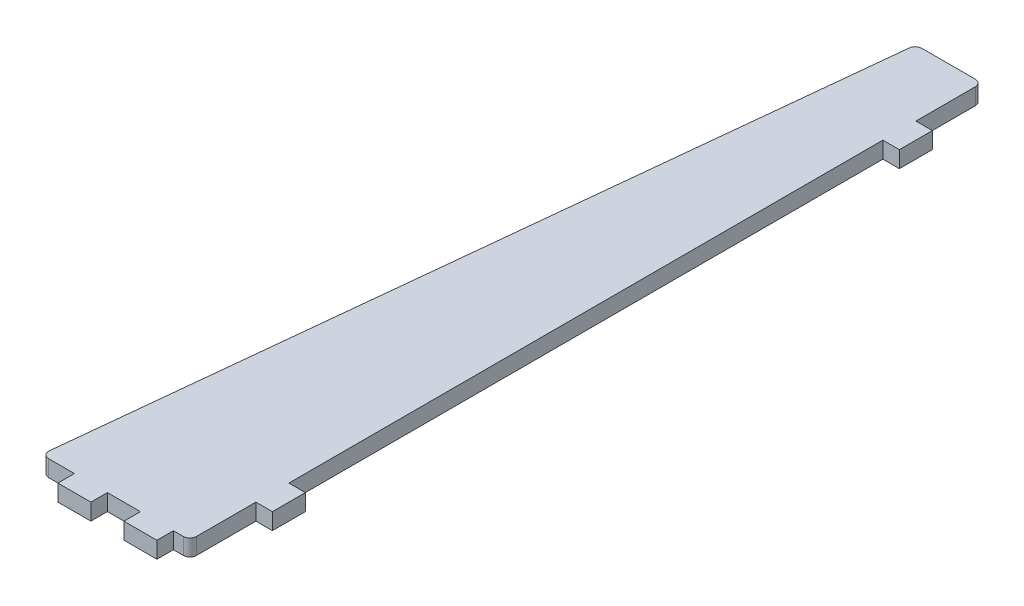
SolidWorks part; units mm, degrees
material "Beech"
ref_plane "Front Plane" through (0, 0, 0) normal (0, 0, 1) x (1, 0, 0)
ref_plane "Top Plane" through (0, 0, 0) normal (0, 1, 0) x (1, 0, 0)
ref_plane "Right Plane" through (0, 0, 0) normal (1, 0, 0) x (0, 0, -1)
sketch "Sketch1" plane through (0, 0, 0) normal (0, 1, 0) x (1, 0, 0)
  line L0 (0, 0) -> (12.7, 0)
  line L1 (12.7, 0) -> (12.7, -6.35)
  line L2 (12.7, -6.35) -> (25.4, -6.35)
  line L3 (25.4, -6.35) -> (25.4, 0)
  line L4 (25.4, 0) -> (38.1, 0)
  line L5 (38.1, 0) -> (38.1, -6.35)
  line L6 (38.1, -6.35) -> (50.8, -6.35)
  line L7 (50.8, -6.35) -> (50.8, 0)
  line L8 (50.8, 0) -> (57.15, 0)
  line L9 (57.15, 0) -> (57.15, 25.4)
  line L10 (57.15, 304.8) -> (31.75, 304.8)
  line L11 (31.75, 304.8) -> (0, 0)
  line L12 (57.15, 25.4) -> (63.5, 25.4)
  line L13 (63.5, 25.4) -> (63.5, 38.1)
  line L14 (63.5, 38.1) -> (57.15, 38.1)
  line L15 (57.15, 38.1) -> (57.15, 266.7)
  line L16 (57.15, 266.7) -> (63.5, 266.7)
  line L17 (63.5, 266.7) -> (63.5, 279.4)
  line L18 (63.5, 279.4) -> (57.15, 279.4)
  line L19 (57.15, 279.4) -> (57.15, 304.8)
  dimension "D1" = 12.7
  dimension "D2" = 6.35
  dimension "D3" = 25.4
  dimension "D4" = 25.4
  dimension "D5" = 12.7
  dimension "D6" = 304.8
  dimension "D7" = 25.4
  dimension "D8" = 25.4
  dimension "D9" = 6.35
extrude "Side Plate" add sketch "Sketch1" along normal blind 6.35
fillet "Fillet1" radius 2.54 4 edges at (57.15, 3.175, 0) (57.15, 3.175, -304.8) (31.75, 3.175, -304.8) (0, 3.175, 0)
equation "\"CageLeftBottomEdge\"=22.11mm"
equation "\"CageLeftTopEdge\"=22.11mm"
equation "\"CageRightBottomEdge\"=21.63mm"
equation "\"CageRightTopEdge\"=21.63mm"
equation "\"CageHeight\"=86.04mm"
equation "\"CageLength\"=73.76mm"
equation "\"CageTopScrewClearance\"=10mm"
equation "\"CageBottomScrewClearance\"=25mm"
equation "\"CageLeftTopDepth\"= 11.65mm"
equation "\"CageLeftBottomDepth\"=11.11mm"
equation "\"CageLeftTopHeight\"=8.56175mm"
equation "\"CageLeftBottomHeight\"=16mm"
equation "\"CageRightTopDepth\"= 11.05mm"
equation "\"CageRightBottomDepth\"=10.58mm"
equation "\"CageRightTopHeight\"=9.6mm"
equation "\"CageRightBottomHeight\"=15.49mm"
equation "\"CageLeftTopChannelDepth\"=2.41908mm"
equation "\"CageLeftBottomChannelDepth\"=2.588mm"
equation "\"CageLeftChannelHeight\"=11.7mm"
equation "\"CageRightTopChannelDepth\"=2.32mm"
equation "\"CageRightBottomChannelDepth\"=2.318mm"
equation "\"CageRightChannelHeight\"=10mm"
equation "\"CageChanRelHeight\"=23.99mm"
equation "\"CageChanRelDepth\"=5.492mm"
equation "\"CageChamberRadius\"=16.261mm"
equation "\"CageScrewDiameter\"=4.8mm"
equation "\"CageSetScrewDiameter\"=3.5mm"
equation "\"CageAxleRadius\"=6.639mm"
equation "\"CageAxleKeyHeight\"=1.619mm"
equation "\"CageAxleKeyWidth\"=2.662mm"
equation "\"CageHoseWindowWidth\"=16.29mm"
equation "\"CageHoseWindowHeight\"=26.5mm"
equation "\"CageHoseWindow-Edge\"=8.89mm"
equation "\"CageScrew-VerticalEdge\"=5.0mm"
equation "\"CageScrew-HorizontalEdge\"=7.5mm"
equation "\"CageScrew-HoseCornerScrewEdge\"=4.45mm"
equation "\"CageAxle-BottomEdge\"=56.05mm"
equation "\"CageAxle-FrontEdge\"=46.03mm"
equation "\"CageBackSetScrew-Axle\"=40mm"
equation "\"CageFrontSetScrew-Axle\"=22mm"
equation "\"CageVelocityWindow-BackEdge\"=34.8mm"
equation "\"CageVelocityWindow-BottomEdge\"=27.55mm"
equation "\"CageVelocityWindowHeight\"=22.29mm"
equation "\"CageVelocityWindowWidth\"=12.61mm"
equation "\"TriggerSlot-BottomEdge\"=6.35mm"
equation "\"TriggerSlot-FrontEdge\"=15mm"
equation "\"TriggerSlotSize\"=6.7mm"
equation "\"TriggerRackOffset\"=.236224in"
equation "\"TriggerSlotSizeInt\"=.25in"
equation "\"MotorMountLegLength\"=.25in"
equation "\"GearOffset\"=.264907in"
equation "\"TriggerSlotSpacing\"=.25in"
equation "\"TriggerMiniSlotWidth\"=3.5mm"
equation "\"TriggerRackWidth\"=6.5mm"
equation "\"whitemotordepth\"=11.27mm"
equation "\"whitemotorbackdepth\"=3.845mm"
equation "\"whitemotoraxledepth\" = 3.5mm"
equation "\"whitemotoraxleoffset\"=11.4mm"
equation "\"whitemotorwidth\"=12.07mm"
equation "\"whitemotorheight\"=16.68mm"
equation "\"whitemotorcylinderlength\" =13.04mm"
equation "\"whitemotorcylinderradius\"=3.845mm"
equation "\"whitemotorcylinderoffset\"=2.35mm"
equation "\"whitemotorcutoutlength\"=1.88mm"
equation "\"whitemotorouterrad\"=5mm"
equation "\"whitemotorinnerrad\"=2.95mm"
equation "\"elasticracklength\"=2in"
equation "\"elasticrackpegsize\"=.25in"
equation "\"elasticrackpegbuffer\"=.125in"
equation "\"elasticrackpegspacing\"=1.76476378in"
equation "\"elasticbaybuffer\"=.25in"
equation "\"elasticdepth\"=.125in"
equation "\"elasticbaydepth\"=.75in"
equation "\"motormountwidth\"=12mm"
equation "\"motormountcornerfillet\"=3mm"
equation "\"pandiscradius\"=14in"
equation "\"towermaterialwidth\"=.25in"
equation "\"towerslotlength\"=.5in"
equation "\"towermarkerspace\"=5in"
equation "\"towerslothorizoffset\"=1in"
equation "\"towerslothorizspacing\"=2in"
equation "\"towerslotvertoffset\"=3in"
equation "\"D1@Sketch1\"=\"towerslotlength\""
equation "\"D2@Sketch1\"=\"towermaterialwidth\""
equation "\"towerupslot\"=1in"
equation "\"D3@Sketch1\"=\"towerupslot\""
equation "\"towerslotvertspacing\"=1in"
equation "\"D4@Sketch1\"=\"towerslotvertspacing\""
equation "\"D5@Sketch1\"=\"towerslotlength\""
equation "\"towerheight\"=12in"
equation "\"D6@Sketch1\"=\"towerheight\""
equation "\"D7@Sketch1\"=\"towerslotlength\"*2"
equation "\"D8@Sketch1\"=\"towerupslot\""
equation "\"D9@Sketch1\"=\"towerslotvertoffset\"-(\"towermarkerspace\"/2)-\"towermaterialwidth\""
equation "\"D1@Side Plate\"=\"towermaterialwidth\""
equation "\"toweraxle\"=.5in"
equation "\"stepperouterrad\"=10mm"
equation "\"stepperscrewsize\"=3.45mm"
equation "\"stepperscrewc2c\"=49.5mm"
equation "\"stepperdepthoffset\"=24mm"
equation "\"stepperhorizoffset\"=22.91mm"
equation "\"shaftslotOD\"=18.8mm"
equation "\"shaftslotID\"=13.28mm"
equation "\"shaftkeywidth\"=2.67mm"
equation "\"shaftkeydepth\"=1.8mm"
equation "\"shaftcollartotaldepth\"=12.5mm"
equation "\"shaftsquaredepth\"=6mm"
equation "\"shaftsetscrewsize\"=3.5mm"
equation "\"shaftkeytightdepth\"=1.85mm"
equation "\"shaftslottightID\"=12.78mm"
equation "\"shaftsetscrewoffset\"=9mm"
equation "\"cagecollartotaldepth\"=10mm"
equation "\"cagecollartotalwidth\"=35mm"
equation "\"cagecollarbasedepth\"=4mm"
equation "\"gearhubintdiam\"=30mm"
equation "\"gearhubintwid\"=15mm"
equation "\"towerspeedwidth\"=2in"
equation "\"towerspeedheight\"=8in"
equation "\"towerspeedgap\"=2in"
equation "\"stepperaxleflat\"=.037in"
equation "\"stepperaxlerad\"=0.11811024in"
equation "\"ajaxaxlesize\"=3.87mm"
equation "\"ajaxinnercut\"=2.3mm"
equation "\"ajaxwidth\"=6.1mm"
equation "\"ajaxdiametral\"=25.8854"
equation "\"ajaxcutoutdepth\"=2.3mm"
equation "\"ajax4020gap\"=29.5mm"
equation "\"ajax4010gap\"=24.5mm"
equation "\"ajax20hubbuffer\"=6.1mm"
equation "\"ajax20hubholeoffset\"=.19685in"
equation "\"ajax20hubholesize\"=.059055in"
equation "\"ajax20cutoutint\"=13.4mm"
equation "\"ajax40hubholesize\"=7.21mm"
equation "\"ajax40hubholeoffset\"=10mm"
equation "\"ajax40hubbuffer\"=8.9mm"
equation "\"ajax40cutoutint\"=32.6mm"
equation "\"bearingpandiscrad\"=6.8in"
equation "\"bearingpandiscang\"=48.75deg"
equation "\"bearingclearholedist\"=4.7345in"
equation "\"bearingclearholesize\"=.5in"
equation "\"bearingclearholeang\"=22.5deg"
equation "\"bearingmountholedist\"=4.25in"
equation "\"bearingwirehole\"=1.5in"
equation "\"no6diam\"=.146in"
equation "\"shortconangle\"=20deg"
equation "\"shortconlen\"=.875in"
equation "\"longconlen\"=1.25in"
equation "\"longconangle\"=15deg"
